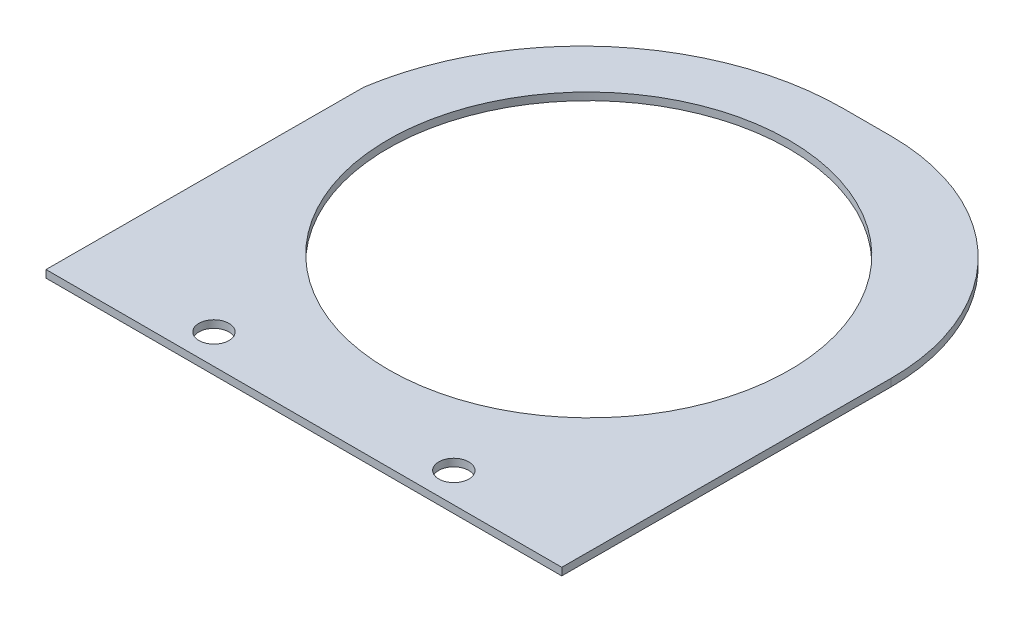
SolidWorks part; units mm, degrees
ref_plane "Front Plane" through (0, 0, 0) normal (0, 0, 1) x (1, 0, 0)
ref_plane "Top Plane" through (0, 0, 0) normal (0, 1, 0) x (1, 0, 0)
ref_plane "Right Plane" through (0, 0, 0) normal (1, 0, 0) x (0, 0, -1)
sketch "Sketch1" plane through (0.0073, -1774.5805, 2.7221) normal (0, 1, -0.0031) x (1, 0, 0)
  line L0 (-3.3195, 108.0964) -> (-3.3195, -120.5036) construction
  line L1 (16.7517, 108.0964) -> (-3.3195, 108.0964)
  line L2 (105.9005, 18.9476) -> (105.9005, -120.5036)
  line L3 (105.9005, -120.5036) -> (-112.5395, -120.5036)
  line L4 (-112.5395, 14.0714) -> (-112.5395, -120.5036)
  line L5 (105.9005, 108.0964) -> (-112.5395, -120.5036) construction
  line L6 (105.9005, -120.5036) -> (-97.2827, 105.4904) construction
  line L7 (-112.5395, 0.1464) -> (105.9005, 0.1464) construction
  line L8 (-3.3195, 0.1464) -> (-112.5395, -37.461) construction
  line L9 (-112.5395, -107.8036) -> (105.9005, -107.8036) construction
  circle A0 centre (-3.3195, 0.1464) radius 84.7725
  circle A1 centre (-3.3195, 0.1464) radius 95.25 construction
  circle A2 centre (-135.2365, -122.4125) radius 6.35
  circle A3 centre (-54.1195, -107.8036) radius 6.35
  circle A4 centre (47.4805, -107.8036) radius 6.35
  circle A5 centre (-3.8601, -22.4211) radius 6.35
  circle A6 centre (17.0467, -186.1921) radius 6.35
  arc A7 (-3.3195, 108.0964) -> (-112.5395, 14.0714) centre (-3.3195, -2.3513) ccw
  arc A8 (16.7517, 108.0964) -> (105.9005, 18.9476) centre (16.7517, 18.9476) cw
  circle A9 centre (-135.2365, -122.4125) radius 6.35 construction
  circle A10 centre (-3.8601, -22.4211) radius 6.35 construction
  point P0 (0.0073, -2.7221)
  point P11 (-3.3195, 0.1464)
  point P30 (-40.6833, -110.3419)
  point P32 (0, 6.35)
  dimension "D3" = 109.22
  dimension "D5" = 190.5
  dimension "D6" = 12.7
  dimension "D7" = 12.7
  dimension "D8" = 12.7
  dimension "D11" = 3
  dimension "D1" = 228.6
  dimension "D2" = 120.65
  dimension "D4" = 19
  dimension "D9" = 50.8
  dimension "D10" = 203.2
extrude "Boss-Extrude1" add sketch "Sketch1" along normal blind 3.175 contours A8 L1 A7 L4 L3 L2 A0 A3 A4 region at (77.561, -1774.8245, -77.0271)
sketch "Sketch2" plane through (-1.0812, -471.4053, 0) normal (0.0046, 1, 0) x (1, -0.0046, 0)
  line L2 (105.6517, -171.3743) -> (-112.7883, -171.3743)
  line L5 (105.6517, -171.3743) -> (105.6517, 110.5657)
  line L6 (105.6517, 110.5657) -> (-112.7883, 110.5657)
  line L10 (-112.7883, 14.9422) -> (-112.7883, -118.0343)
  line L11 (-112.7883, -118.0343) -> (105.6517, -118.0343)
  line L12 (105.6517, -118.0343) -> (105.6517, 21.6657)
  line L13 (16.7517, 110.5657) -> (-3.5683, 110.5657)
  line L14 (-112.7883, -171.3743) -> (-112.7883, 110.5657)
  line L15 (105.6517, -171.3743) -> (-135.6483, -171.3743)
  line L16 (105.6517, -171.3743) -> (105.6517, 111.6071)
  line L17 (105.6517, 111.6071) -> (-135.6483, 111.6071)
  line L18 (-135.6483, -171.3743) -> (-135.6483, 111.6071)
  point P0 (0, 0)
  dimension "D2" = 53.34
  dimension "D5" = 241.3
  dimension "D6" = 282.9814
